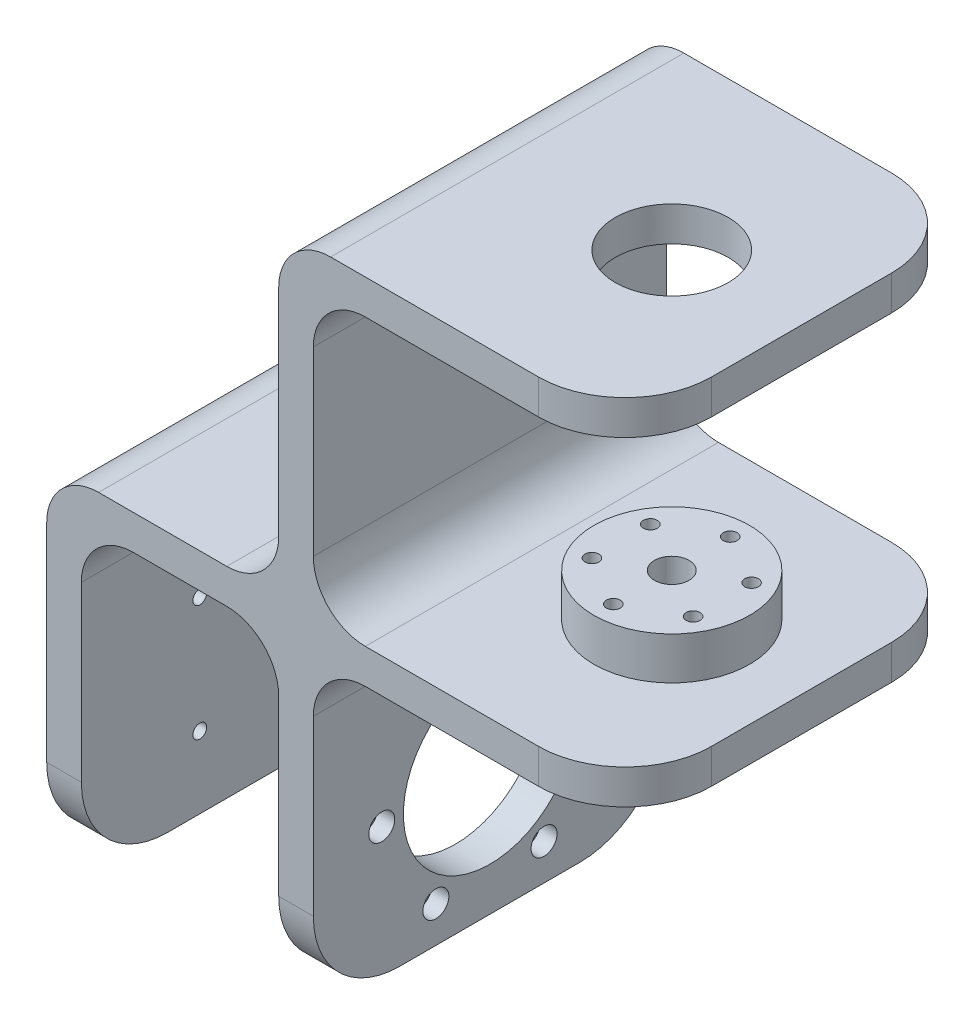
SolidWorks part; units mm, degrees
material "PETG-CF"
ref_plane "前视基准面" through (0, 0, 0) normal (0, 0, 1) x (1, 0, 0)
ref_plane "上视基准面" through (0, 0, 0) normal (0, 1, 0) x (1, 0, 0)
ref_plane "右视基准面" through (0, 0, 0) normal (1, 0, 0) x (0, 0, -1)
other "Configuration Table"
sketch "草图1" plane through (0, 0, 0) normal (0, 1, 0) x (1, 0, 0)
  line L1 (40, -40.8) -> (-40, -40.8)
  line L2 (40, -40.8) -> (40, 40.8)
  line L3 (40, 40.8) -> (-40, 40.8)
  line L4 (-40, -40.8) -> (-40, 40.8)
  line L5 (40, -40.8) -> (-40, 40.8) construction
  line L6 (40, 40.8) -> (-40, -40.8) construction
  point P0 (0, 0)
  dimension "D1" = 81.6
  dimension "D2" = 80
extrude "凸台-拉伸1" add sketch "草图1" along normal blind 8
sketch "草图2" plane through (0, 8, 0) normal (0, 1, 0) x (1, 0, 0)
  line L0 (-40, 40.8) -> (-40, -40.8) construction
  line L1 (-32, -40.8) -> (-40, -40.8)
  line L2 (-32, -40.8) -> (-32, 40.8)
  line L3 (-32, 40.8) -> (-40, 40.8)
  line L4 (-40, -40.8) -> (-40, 40.8)
  line L5 (-32, -40.8) -> (-40, 40.8) construction
  line L6 (-32, 40.8) -> (-40, -40.8) construction
  line L7 (40, 40.8) -> (-40, 40.8) construction
  line L8 (-40, -40.8) -> (40, -40.8) construction
  point P0 (-36, 0)
  dimension "D1" = 8
extrude "凸台-拉伸2" add sketch "草图2" along normal blind 52.9
sketch "草图10" plane through (0, 60.9, 0) normal (0, 1, 0) x (1, 0, 0)
  line L0 (-40, -40.8) -> (-40, 40.8) construction
  line L1 (-32, -40.8) -> (-40, -40.8)
  line L2 (-32, -40.8) -> (-32, 40.8)
  line L3 (-32, 40.8) -> (-40, 40.8)
  line L4 (-40, -40.8) -> (-40, 40.8)
  line L5 (-32, -40.8) -> (-40, 40.8) construction
  line L6 (-32, 40.8) -> (-40, -40.8) construction
  line L7 (-32, 40.8) -> (-40, 40.8) construction
  line L8 (-32, -40.8) -> (-32, 40.8) construction
  line L9 (-32, -40.8) -> (-40, -40.8) construction
  point P0 (-36, 0)
extrude "凸台-拉伸7" add sketch "草图10" along normal blind 13
sketch "草图11" plane through (0, 73.9, 0) normal (0, 1, 0) x (1, 0, 0)
  line L0 (-40, -40.8) -> (-40, 40.8) construction
  line L1 (40, -40.8) -> (-40, -40.8)
  line L2 (40, -40.8) -> (40, 40.8)
  line L3 (40, 40.8) -> (-40, 40.8)
  line L4 (-40, -40.8) -> (-40, 40.8)
  line L5 (40, -40.8) -> (-40, 40.8) construction
  line L6 (40, 40.8) -> (-40, -40.8) construction
  line L7 (40, -40.8) -> (40, 40.8) construction
  line L8 (40, 40.8) -> (-40, 40.8) construction
  line L9 (40, -40.8) -> (-40, -40.8) construction
  point P0 (0, 0)
extrude "凸台-拉伸8" add sketch "草图11" along normal blind 8
sketch "草图6" plane through (0, 8, 0) normal (0, 1, 0) x (1, 0, 0)
  line L1 (40, 40.8) -> (-40, 40.8) construction
  line L3 (40, -40.8) -> (40, 40.8) construction
  circle A0 centre (10, 0) radius 18
  point P2 (0, 40.8)
  point P3 (40, 0)
  point P6 (10, 40.8)
  dimension "D3" = 36
  dimension "D1" = 10
extrude "凸台-拉伸4" add sketch "草图6" along normal blind 9.8
sketch "草图4" plane through (0, 8, 0) normal (0, 1, 0) x (1, 0, 0)
  line L2 (40, -40.8) -> (40, 40.8) construction
  line L3 (40, 40.8) -> (-40, 40.8) construction
  circle A0 centre (10, 0) radius 13.5 construction
  circle A1 centre (10, 13.5) radius 1.6
  circle A2 centre (21.6913, 6.75) radius 1.6
  circle A3 centre (21.6913, -6.75) radius 1.6
  circle A4 centre (10, -13.5) radius 1.6
  circle A5 centre (-1.6913, -6.75) radius 1.6
  circle A6 centre (-1.6913, 6.75) radius 1.6
  circle A7 centre (10, 0) radius 4
  point P2 (40, 0)
  point P3 (10, 40.8)
  point P9 (0, 40.8)
  point P21 (10, 0)
  dimension "D1" = 27
  dimension "D4" = 3.2
  dimension "D6" = 8
  dimension "D2" = 10
  dimension "D5" = 6
extrude "切除-拉伸1" cut sketch "草图4" against normal through all and the other way up to next
sketch "草图12" plane through (0, 73.9, 0) normal (0, -1, 0) x (-1, 0, 0)
  circle A0 centre (-10, 0) radius 13.05
  dimension "D1" = 26.1
extrude "切除-拉伸3" cut sketch "草图12" against normal up to next
sketch "草图21" plane through (0, 0, 0) normal (0, -1, 0) x (-1, 0, 0)
  circle A0 centre (-10, -13.5) radius 3
  circle A1 centre (-21.6913, -6.75) radius 3
  circle A2 centre (-21.6913, 6.75) radius 3
  circle A3 centre (-10, 13.5) radius 3
  circle A4 centre (1.6913, 6.75) radius 3
  circle A5 centre (1.6913, -6.75) radius 3
  point P16 (-10, 0)
  dimension "D1" = 6
  dimension "D2" = 6
extrude "切除-拉伸10" cut sketch "草图21" against normal blind 4
sketch "Sketch1" plane through (0, 0, 0) normal (0, -1, 0) x (-1, 0, 0)
  line L0 (-40, 40.8) -> (40, 40.8) construction
  line L1 (40, -40.8) -> (32, -40.8)
  line L2 (40, -40.8) -> (40, 40.8)
  line L3 (40, 40.8) -> (32, 40.8)
  line L4 (32, -40.8) -> (32, 40.8)
  dimension "D1" = 8
extrude "Boss-Extrude1" add sketch "Sketch1" along normal blind 72
sketch "Sketch2" plane through (-40, 0, 0) normal (-1, 0, 0) x (0, 0, 1)
  line L0 (-40.8, 81.9) -> (-40.8, -72) construction
  line L1 (-40.8, 0) -> (40.8, 0)
  line L2 (-40.8, 0) -> (-40.8, 8)
  line L3 (-40.8, 8) -> (40.8, 8)
  line L4 (40.8, 0) -> (40.8, 8)
  line L5 (40.8, 81.9) -> (40.8, -72) construction
  dimension "D1" = 8
extrude "Boss-Extrude2" add sketch "Sketch2" along normal blind 53.6
sketch "Sketch3" plane through (0, 0, 0) normal (0, -1, 0) x (-1, 0, 0)
  line L0 (93.6, 40.8) -> (40, 40.8) construction
  line L1 (93.6, -40.8) -> (85.6, -40.8)
  line L2 (93.6, -40.8) -> (93.6, 40.8)
  line L3 (93.6, 40.8) -> (85.6, 40.8)
  line L4 (85.6, -40.8) -> (85.6, 40.8)
  dimension "D1" = 8
extrude "Boss-Extrude3" add sketch "Sketch3" along normal up to surface (72 mm away) up to face at (-36, -72, 0)
sketch "Sketch4" plane through (-32, 0, 0) normal (1, 0, 0) x (0, 0, -1)
  line L0 (40.8, -72) -> (-40.8, -72) construction
  circle A0 centre (0, -42) radius 20
  circle A2 centre (25, -42) radius 1.6
  circle A3 centre (0, -42) radius 25 construction
  circle A4 centre (12.5, -63.6506) radius 1.6
  circle A5 centre (-12.5, -63.6506) radius 1.6
  circle A6 centre (-25, -42) radius 1.6
  circle A7 centre (-12.5, -20.3494) radius 1.6
  circle A8 centre (12.5, -20.3494) radius 1.6
  point P20 (0, -42)
  dimension "D2" = 40
  dimension "D3" = 3.2
  dimension "D4" = 50
  dimension "D1" = 30
  dimension "D5" = 6
extrude "Cut-Extrude1" cut sketch "Sketch4" against normal up to next
sketch "Sketch5" plane through (-85.6, 0, 0) normal (1, 0, 0) x (0, 0, -1)
  line L0 (40.8, -72) -> (-40.8, -72) construction
  line L1 (0, 0) -> (0, -42) construction
  line L2 (-13.435, -28.565) -> (0, -42) construction
  circle A0 centre (0, -42) radius 19 construction
  circle A1 centre (-13.435, -28.565) radius 1.6
  circle A2 centre (13.435, -28.565) radius 1.6
  circle A3 centre (13.435, -55.435) radius 1.6
  circle A4 centre (-13.435, -55.435) radius 1.6
  point P17 (0, -42)
  dimension "D1" = 38
  dimension "D3" = 3.2
  dimension "D2" = 30
  dimension "D4" = 45
  dimension "D5" = 4
extrude "Cut-Extrude2" cut sketch "Sketch5" against normal up to next
sketch "Sketch6" plane through (-93.6, 0, 0) normal (-1, 0, 0) x (0, 0, 1)
  circle A0 centre (-13.435, -28.565) radius 3
  circle A1 centre (13.435, -28.565) radius 3
  circle A2 centre (13.435, -55.435) radius 3
  circle A3 centre (-13.435, -55.435) radius 3
  point P12 (0, -42)
  dimension "D1" = 6
  dimension "D2" = 4
extrude "Cut-Extrude3" cut sketch "Sketch6" against normal blind 4
sketch "Sketch7" plane through (-32, 0, 0) normal (1, 0, 0) x (0, 0, -1)
  circle A0 centre (-12.5, -20.3494) radius 3
  circle A1 centre (12.5, -20.3494) radius 3
  circle A2 centre (25, -42) radius 3
  circle A3 centre (12.5, -63.6506) radius 3
  circle A4 centre (-12.5, -63.6506) radius 3
  circle A5 centre (-25, -42) radius 3
  point P15 (0, -42)
  dimension "D1" = 6
  dimension "D2" = 6
extrude "Cut-Extrude4" cut sketch "Sketch7" against normal blind 4
fillet "Fillet1" radius 12 8 edges at (-85.6, 0, 0) (-40, 0, 0) (-32, 73.9, 0) (-32, 8, 0) (-32, 0, 0) (-40, 8, 0) (-40, 81.9, 0) (-93.6, 8, 0)
fillet "Fillet2" radius 20 8 edges at (-89.6, -72, 40.8) (-89.6, -72, -40.8) (-36, -72, 40.8) (-36, -72, -40.8) (40, 4, 40.8) (40, 4, -40.8) (40, 77.9, 40.8) (40, 77.9, -40.8)
